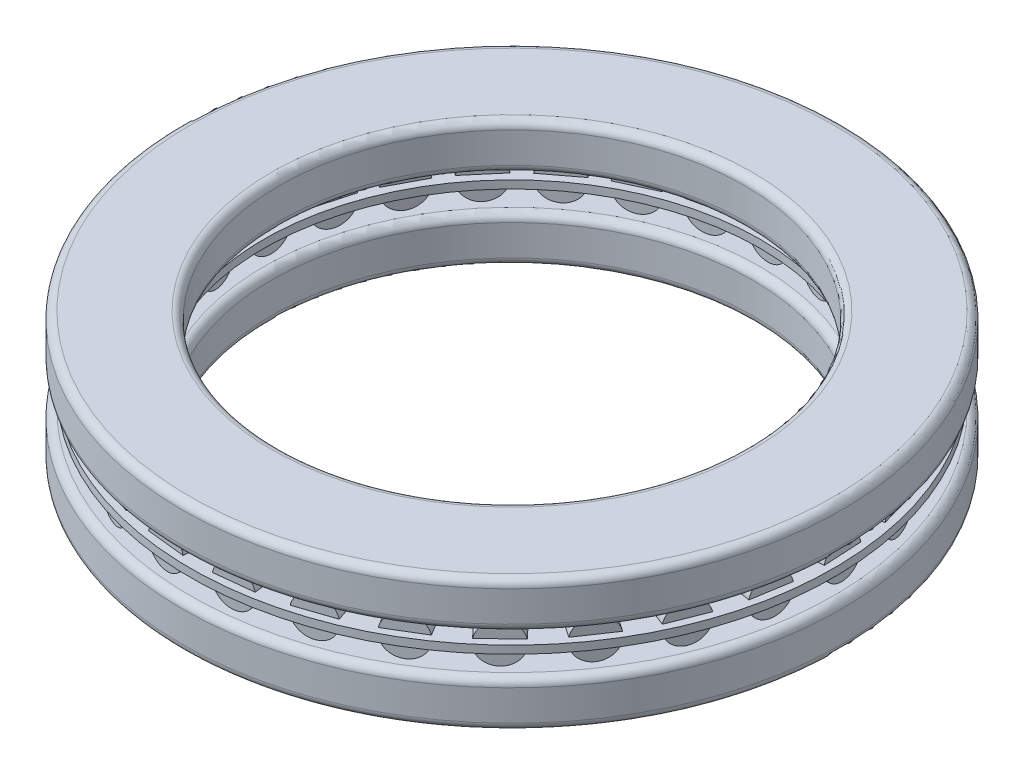
SolidWorks part; units mm, degrees
ref_plane "前视基准面" through (0, 0, 0) normal (0, 0, 1) x (1, 0, 0)
ref_plane "上视基准面" through (0, 0, 0) normal (0, 1, 0) x (1, 0, 0)
ref_plane "右视基准面" through (0, 0, 0) normal (1, 0, 0) x (0, 0, -1)
sketch "草图1" plane through (0, 0, 0) normal (1, 0, 0) x (0, 0, -1)
  line L0 (0, 40.2628) -> (0, 0) construction
  line L1 (0, 0) -> (70.6499, 0) construction
  line L2 (0, 0) -> (0, -1) construction
  line L3 (32, 2.975) -> (41.5, 2.975)
  line L4 (31, 1.975) -> (31, -1.975)
  line L5 (32, -2.975) -> (41.5, -2.975)
  line L6 (42.5, 1.975) -> (42.5, -1.975)
  line L7 (31, 14.025) -> (41.5, 14.025)
  line L8 (30, 13.025) -> (30, 9.075)
  line L9 (31, 8.075) -> (41.5, 8.075)
  line L10 (42.5, 13.025) -> (42.5, 9.075)
  line L11 (41.5, 5.525) -> (32, 5.525) construction
  line L12 (41.5, 6.035) -> (32, 6.035)
  line L13 (41.5, 6.035) -> (41.5, 5.015)
  line L14 (41.5, 5.015) -> (32, 5.015)
  line L15 (32, 6.035) -> (32, 5.015)
  arc A0 (41.5, -2.975) -> (42.5, -1.975) centre (41.5, -1.975) ccw
  arc A1 (41.5, 2.975) -> (42.5, 1.975) centre (41.5, 1.975) cw
  arc A2 (31, -1.975) -> (32, -2.975) centre (32, -1.975) ccw
  arc A3 (32, 2.975) -> (31, 1.975) centre (32, 1.975) ccw
  arc A4 (41.5, 14.025) -> (42.5, 13.025) centre (41.5, 13.025) cw
  arc A5 (41.5, 8.075) -> (42.5, 9.075) centre (41.5, 9.075) ccw
  arc A6 (30, 9.075) -> (31, 8.075) centre (31, 9.075) ccw
  arc A7 (31, 14.025) -> (30, 13.025) centre (31, 13.025) ccw
  dimension "D3" = 1
  dimension "D1" = 62
  dimension "T" = 17
  dimension "D" = 85
  dimension "D2" = 5.1
  dimension "(d1)" = 85
  dimension "(d)" = 60
  dimension "r" = 1
  dimension "D4" = 1.02
sketch "草图2" plane through (0, 0, 0) normal (1, 0, 0) x (0, 0, -1)
  line L0 (32, 2.975) -> (41.5, 2.975) construction
  line L1 (42.5, 1.975) -> (42.5, -1.975) construction
  line L2 (32, -2.975) -> (41.5, -2.975) construction
  line L3 (31, 1.975) -> (31, -1.975) construction
  line L4 (32, 2.975) -> (41.5, 2.975)
  line L5 (42.5, 1.975) -> (42.5, -1.975)
  line L6 (32, -2.975) -> (41.5, -2.975)
  line L7 (31, 1.975) -> (31, -1.975)
  line L8 (0, 0) -> (0, 14.9997) construction
  line L9 (0, 40.2628) -> (0, 0) construction
  arc A0 (42.5, 1.975) -> (41.5, 2.975) centre (41.5, 1.975) ccw construction
  arc A1 (41.5, -2.975) -> (42.5, -1.975) centre (41.5, -1.975) ccw construction
  arc A2 (31, -1.975) -> (32, -2.975) centre (32, -1.975) ccw construction
  arc A3 (32, 2.975) -> (31, 1.975) centre (32, 1.975) ccw construction
  arc A4 (42.5, 1.975) -> (41.5, 2.975) centre (41.5, 1.975) ccw
  arc A5 (41.5, -2.975) -> (42.5, -1.975) centre (41.5, -1.975) ccw
  arc A6 (31, -1.975) -> (32, -2.975) centre (32, -1.975) ccw
  arc A7 (32, 2.975) -> (31, 1.975) centre (32, 1.975) ccw
revolve "旋转1" add sketch "草图2" angle 360 mid plane about L8
sketch "草图3" plane through (0, 0, 0) normal (1, 0, 0) x (0, 0, -1)
  line L0 (31, 14.025) -> (41.5, 14.025) construction
  line L1 (42.5, 13.025) -> (42.5, 9.075) construction
  line L2 (31, 8.075) -> (41.5, 8.075) construction
  line L3 (30, 13.025) -> (30, 9.075) construction
  line L4 (31, 14.025) -> (41.5, 14.025)
  line L5 (42.5, 13.025) -> (42.5, 9.075)
  line L6 (31, 8.075) -> (41.5, 8.075)
  line L7 (30, 13.025) -> (30, 9.075)
  line L8 (0, 0) -> (0, 10.4732) construction
  line L9 (0, 40.2628) -> (0, 0) construction
  arc A0 (42.5, 13.025) -> (41.5, 14.025) centre (41.5, 13.025) ccw construction
  arc A1 (41.5, 8.075) -> (42.5, 9.075) centre (41.5, 9.075) ccw construction
  arc A2 (30, 9.075) -> (31, 8.075) centre (31, 9.075) ccw construction
  arc A3 (31, 14.025) -> (30, 13.025) centre (31, 13.025) ccw construction
  arc A4 (42.5, 13.025) -> (41.5, 14.025) centre (41.5, 13.025) ccw
  arc A5 (41.5, 8.075) -> (42.5, 9.075) centre (41.5, 9.075) ccw
  arc A6 (30, 9.075) -> (31, 8.075) centre (31, 9.075) ccw
  arc A7 (31, 14.025) -> (30, 13.025) centre (31, 13.025) ccw
revolve "旋转2" add sketch "草图3" angle 360 mid plane about L8
ref_plane "基准面1" through (0, 5.525, 0) normal (0, -1, 0) x (1, 0, 0)
sketch "草图7" plane through (0, 0, 0) normal (1, 0, 0) x (0, 0, -1)
  line L0 (41.5, 5.015) -> (32, 5.015) construction
  line L1 (32, 6.035) -> (32, 5.015) construction
  line L2 (41.5, 6.035) -> (32, 6.035) construction
  line L3 (41.5, 6.035) -> (41.5, 5.015) construction
  line L4 (41.5, 5.015) -> (32, 5.015)
  line L5 (32, 6.035) -> (32, 5.015)
  line L6 (41.5, 6.035) -> (32, 6.035)
  line L7 (41.5, 6.035) -> (41.5, 5.015)
  line L8 (0, 0) -> (0, 12.5332) construction
  line L9 (0, 40.2628) -> (0, 0) construction
revolve "旋转4" add sketch "草图7" angle 360 mid plane about L8
sketch "草图4" plane through (0, 5.525, 0) normal (0, -1, 0) x (1, 0, 0)
  line L0 (0, 0) -> (0, -19.4594) construction
  line L1 (0, 0) -> (0, -70.6499) construction
  line L3 (0, -33) -> (-2.55, -33)
  line L4 (0, -33) -> (0, -40.5)
  line L5 (0, -40.5) -> (-2.55, -40.5)
  line L6 (-2.55, -33) -> (-2.55, -40.5)
  line L7 (0, -41.5) -> (0, -32) construction
  dimension "D1" = 5.1
  dimension "D2" = 1
  dimension "D3" = 1
revolve "切除-旋转1" cut sketch "草图4<3>" angle 360 mid plane about L0
sketch "草图4<3>" plane through (0, 5.525, 0) normal (0, -1, 0) x (1, 0, 0) same geometry as "草图4"
pattern_circular "阵列(圆周)2" count 29 over 360 of "切除-旋转1"
revolve "旋转3" add sketch "草图4" angle 360 mid plane about L0
pattern_circular "阵列(圆周)1" count 29 over 360 of bodies 103 116
